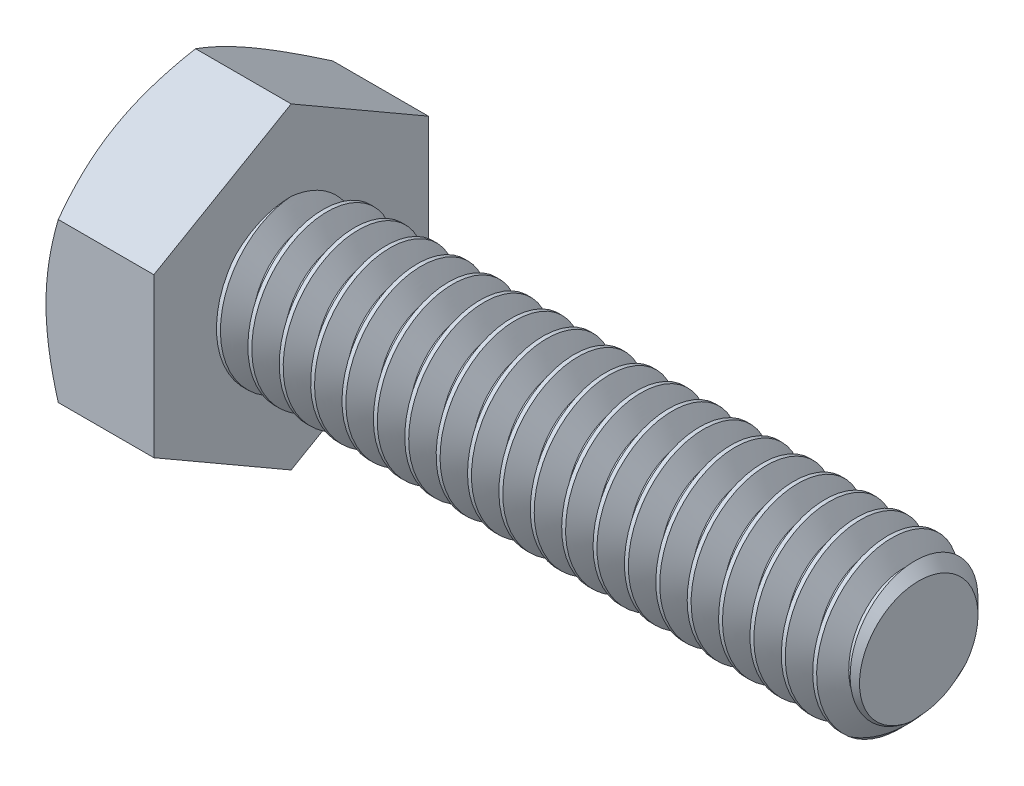
SolidWorks part; units mm, degrees
ref_plane "Front Plane" through (0, 0, 0) normal (0, 0, 1) x (1, 0, 0)
ref_plane "Top Plane" through (0, 0, 0) normal (0, 1, 0) x (1, 0, 0)
ref_plane "Right Plane" through (0, 0, 0) normal (1, 0, 0) x (0, 0, -1)
sketch "Sketch1" plane through (0, 0, 0) normal (0, 0, 1) x (1, 0, 0)
  line L0 (-14.8828, 0) -> (14.8828, 0) construction
  line L1 (14.8828, 3.175) -> (14.8828, -3.175) construction
  line L2 (-10.5172, 5.5562) -> (-10.5172, -5.5562) construction
  line L3 (-14.8828, 5.5562) -> (-14.8828, -5.5562) construction
  point P9 (-10.5172, 0)
  point P10 (10.4378, -3.175)
  dimension "D1" = 4.445
  dimension "Screw Dia" = 6.35
  dimension "Hex" = 11.1125
  dimension "Head Ht" = 4.3656
  dimension "Screw Lenght" = 25.4
ref_plane "Plane2" through (14.8828, 0, 0) normal (1, 0, 0) x (0, 0, -1)
sketch "Sketch5" plane through (14.8828, 0, 0) normal (1, 0, 0) x (0, 0, -1)
  circle A0 centre (0, 0) radius 3.175
extrude "Boss-Extrude3" add sketch "Sketch5" against normal up to vertex (25.4 mm away) up to point (-10.5172, 0, 0)
sketch "Sketch9" plane through (14.8828, 0, 0) normal (1, 0, 0) x (0, 0, -1)
  circle A1 centre (0, 0) radius 3.175
  circle A2 centre (0, 0) radius 3.175
  dimension "D1" = 0
curve "Helix/Spiral1" pitch 1.27 height 26.67 turns 21 parameters "Pitch"=1.27
chamfer "Chamfer1" distance 0.7772 angle 45 1 edges at (14.8828, 0, -3.175)
sketch "Sketch10" plane through (0, 0, 0) normal (0, 0, 1) x (1, 0, 0)
  line L0 (14.8828, 3.175) -> (15.3591, 2.3501)
  line L1 (15.3591, 2.3501) -> (15.5178, 2.3501)
  line L2 (15.5178, 2.3501) -> (15.9941, 3.175)
  line L3 (14.8828, 3.175) -> (15.9941, 3.175)
  line L4 (15.4384, 3.175) -> (15.4384, 2.3501) construction
  line L5 (15.1209, 2.7626) -> (15.7559, 2.7626) construction
  dimension "D1" = 60
  dimension "D2" = 0.1588
  dimension "D3" = 0.635
sweep "Cut-Sweep1" cut profiles "Sketch10" path "Helix/Spiral1"
sketch "Sketch6" plane through (-10.5172, 0, 0) normal (-1, 0, 0) x (0, 0, 1)
  line L0 (0, 5.5562) -> (0, -5.5562) construction
  line L1 (5.5563, 3.2079) -> (0, 6.4158)
  line L2 (0, 6.4158) -> (-5.5562, 3.2079)
  line L3 (-5.5562, 3.2079) -> (-5.5562, -3.2079)
  line L4 (-5.5562, -3.2079) -> (0, -6.4158)
  line L5 (0, -6.4158) -> (5.5563, -3.2079)
  line L6 (5.5563, -3.2079) -> (5.5563, 3.2079)
  circle A0 centre (0, 0) radius 5.5563 construction
extrude "Boss-Extrude4" add sketch "Sketch6" along normal up to vertex (4.3656 mm away) up to point (-14.8828, -5.5562, 0)
sketch "Sketch7" plane through (-14.8828, 0, 0) normal (-1, 0, 0) x (0, 0, 1)
  circle A0 centre (0, 0) radius 5.5563 construction
  circle A1 centre (0, 0) radius 5.5563
sketch "Sketch8" plane through (-14.8828, 0, 0) normal (-1, 0, 0) x (0, 0, 1)
  circle A0 centre (0, 0) radius 5.5563 construction
  circle A1 centre (0, 0) radius 5.5563
extrude "Cut-Extrude3" cut sketch "Sketch8" against normal through all draft 60 flip side to cut
sketch "Sketch12" plane through (-14.8828, 0, 0) normal (-1, 0, 0) x (0, 0, 1)
  line L0 (0, 4.2783) -> (0, 2.3892) construction
  line L1 (0.1667, 4.2783) -> (0.1667, 2.3892)
  line L2 (-0.1667, 4.2783) -> (-0.1667, 2.3892)
  line L3 (0, 3.175) -> (0, -3.175) construction
  arc A0 (0.1667, 4.2783) -> (-0.1667, 4.2783) centre (0, 4.2783) ccw
  arc A1 (-0.1667, 2.3892) -> (0.1667, 2.3892) centre (0, 2.3892) ccw
  circle A3 centre (0, 0) radius 2.2225 construction
  circle A4 centre (0, 0) radius 4.445 construction
  point P2 (0, 3.3337)
  dimension "D1" = 4.445
  dimension "D3" = 8.89
  dimension "D2" = 0.3334
extrude "Cut-Extrude4" cut sketch "Sketch12" against normal blind 0.254
pattern_circular "CirPattern1" count 3 over 360 about axis through (0, 0, 0) along (1, 0, 0) of "Cut-Extrude4"
equation "\"D2@Sketch10\" = \"Pitch@Helix/Spiral1\"*.125"
equation "\"D3@Sketch10\" = \"Pitch@Helix/Spiral1\"*.5"
equation "\"D1@Chamfer1\" = \"Pitch@Helix/Spiral1\"*.612"
equation "\"D1@Sketch12\" = \"Hex@Sketch1\"*.4"
equation "\"D3@Sketch12\" = \"Hex@Sketch1\"*.8"
equation "\"D2@Sketch12\" = \"Hex@Sketch1\"*.03"
equation "\"D1@Sketch1\" = \"Pitch@Helix/Spiral1\"*3.5"
equation "\"D3@Helix/Spiral1\" = \"Screw Lenght@Sketch1\"+\"Pitch@Helix/Spiral1\""
